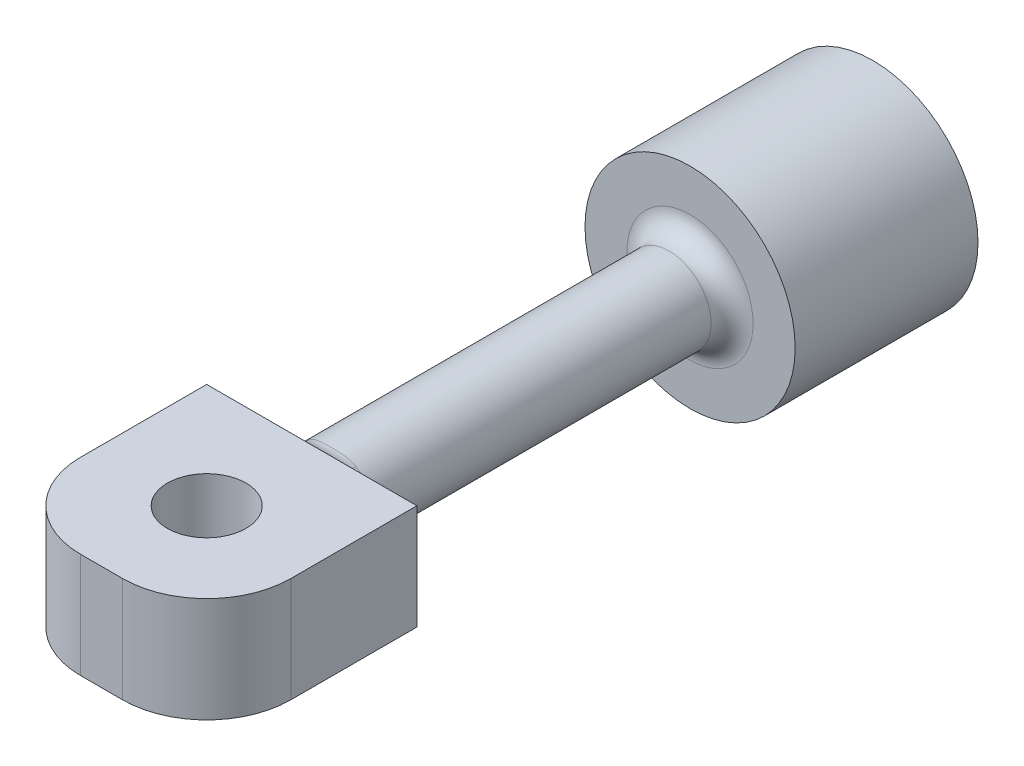
SolidWorks part; units mm, degrees
material "1023 Carbon Steel Sheet (SS)"
ref_plane "Front Plane" through (0, 0, 0) normal (0, 0, 1) x (1, 0, 0)
ref_plane "Top Plane" through (0, 0, 0) normal (0, 1, 0) x (1, 0, 0)
ref_plane "Right Plane" through (0, 0, 0) normal (1, 0, 0) x (0, 0, -1)
sketch "Sketch1" plane through (0, 0, 0) normal (0, 0, 1) x (1, 0, 0)
  line L0 (0, 39.2929) -> (0, -35.5752) construction
  circle A0 centre (0, 0) radius 6.35
  dimension "D1" = 12.7
extrude "Boss-Extrude1" add sketch "Sketch1" along normal blind 11.049
sketch "Sketch2" plane through (0, 0, 11.049) normal (0, 0, 1) x (1, 0, 0)
  circle A0 centre (0, 0) radius 2.54
  dimension "D1" = 5.08
extrude "Boss-Extrude2" add sketch "Sketch2" along normal blind 22.86
sketch "Sketch3" plane through (0, 0, 33.909) normal (0, 0, 1) x (1, 0, 0)
  line L1 (-6.35, 3.175) -> (6.35, 3.175)
  line L2 (-6.35, 3.175) -> (-6.35, -3.175)
  line L3 (-6.35, -3.175) -> (6.35, -3.175)
  line L4 (6.35, 3.175) -> (6.35, -3.175)
  line L5 (-6.35, 3.175) -> (6.35, -3.175) construction
  line L6 (-6.35, -3.175) -> (6.35, 3.175) construction
  point P0 (0, 0)
  dimension "D1" = 12.7
  dimension "D2" = 6.35
extrude "Boss-Extrude3" add sketch "Sketch3" along normal blind 12.7
fillet "Fillet1" radius 5.08 2 edges at (-6.35, 0, 46.609) (6.35, 0, 46.609)
sketch "Sketch4" plane through (0, -3.175, 0) normal (0, -1, 0) x (1, 0, 0)
  line L0 (-6.35, 33.909) -> (6.35, 33.909) construction
  line L1 (6.35, 41.529) -> (6.35, 33.909) construction
  circle A0 centre (0, 40.259) radius 2.3749
  dimension "D1" = 4.7498
  dimension "D2" = 6.35
  dimension "D3" = 6.35
extrude "Cut-Extrude1" cut sketch "Sketch4" against normal blind 12.7
fillet "Fillet2" radius 1.27 2 edges at (2.54, 0, 11.049) (2.54, 0, 33.909)
